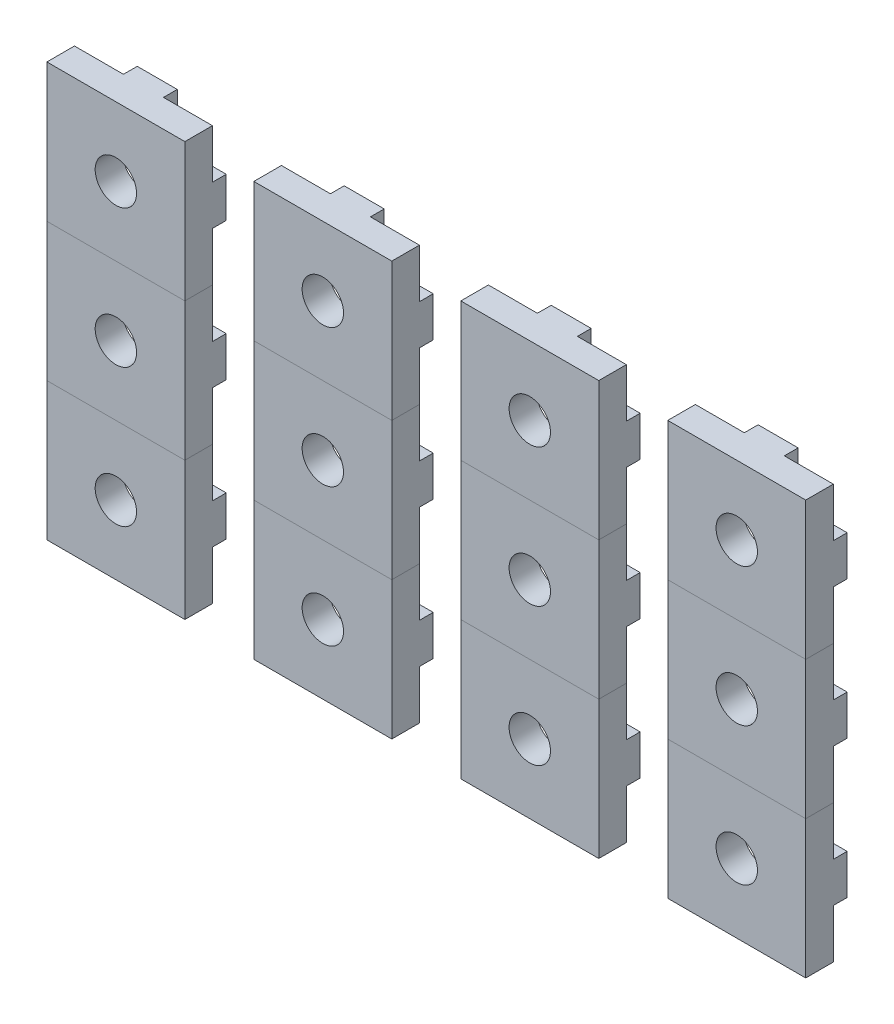
SolidWorks part; units mm, degrees
note: '?' marks a value the reader was unsure of.
ref_plane "Front Plane" through (0, 0, 0) normal (0, 0, 1) x (1, 0, 0)
ref_plane "Top Plane" through (0, 0, 0) normal (0, 1, 0) x (1, 0, 0)
ref_plane "Right Plane" through (0, 0, 0) normal (1, 0, 0) x (0, 0, -1)
ref_axis "Axis1" through (0, 0, -1.2) along (0, 0, 1)?
sketch "Sketch1" plane through (0, 0, 0) normal (0, 0, 1) x (1, 0, 0)
  line L1 (-5, -5) -> (5, -5)
  line L2 (-5, -5) -> (-5, 5)
  line L3 (-5, 5) -> (5, 5)
  line L4 (5, -5) -> (5, 5)
  line L5 (-5, -5) -> (5, 5) construction
  line L6 (-5, 5) -> (5, -5) construction
  circle A0 centre (0, 0) radius 1.5
  point P0 (0, 0)
  dimension "D3" = 3
  dimension "D1" = 10
  dimension "D2" = 10
extrude "Main" add sketch "Sketch1" along normal blind 2
sketch "Sketch2" plane through (0, 0, 0) normal (0, 0, -1) x (-1, 0, 0)
  line L0 (-5, 1.45) -> (-3.9, 1.45)
  line L1 (-5, -5) -> (-5, 5) construction
  line L2 (-3.9, 1.45) -> (-3.9, 3)
  line L3 (-3.9, -1.45) -> (-5, -1.45)
  line L4 (-5, 1.45) -> (-5, -1.45)
  line L5 (-3.9, 3) -> (-2.1, 0.95)
  line L6 (-2.1, 0.95) -> (-2.1, -0.95)
  line L7 (-2.1, -0.95) -> (-3.9, -3)
  line L8 (-3.9, -3) -> (-3.9, -1.45)
  line L9 (-5, 5) -> (5, 5) construction
  point P5 (-2.1, 0)
  dimension "D1" = 2.9
  dimension "D2" = 1.1
  dimension "D3" = 1.9
  dimension "D4" = 2.1
  dimension "D5" = 2
extrude "AntiRotationSystem" add sketch "Sketch2" along normal blind 1
pattern_circular "CirPattern1" count 4 over 360 about axis through (0, 0, 0) along (0, 0, 1) of "AntiRotationSystem"
pattern_linear "LPattern1" count 3 spacing 10 along (0, -1, 0) of bodies 103
pattern_linear "LPattern2" count 4 spacing 15 along (-1, 0, 0) of bodies 103 107 110
